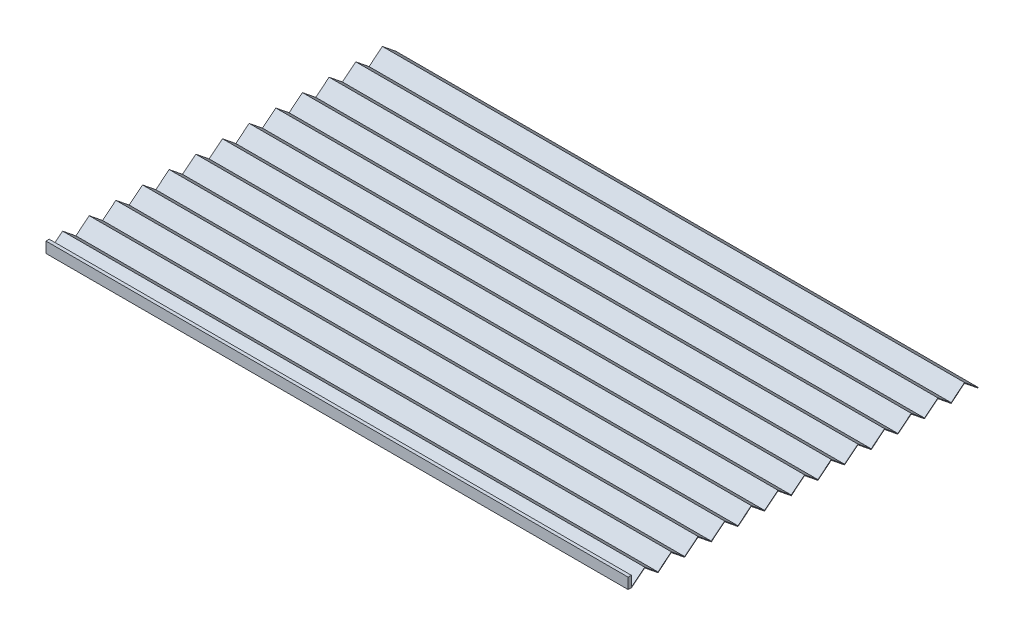
SolidWorks part; units mm, degrees
ref_plane "Front Plane" through (0, 0, 0) normal (0, 0, 1) x (1, 0, 0)
ref_plane "Top Plane" through (0, 0, 0) normal (0, 1, 0) x (1, 0, 0)
ref_plane "Right Plane" through (0, 0, 0) normal (1, 0, 0) x (0, 0, -1)
sketch "Sketch2" plane through (0, 0, 0) normal (0, 0, 1) x (1, 0, 0)
  line L1 (-270, 10) -> (270, 10)
  line L2 (-270, 10) -> (-270, 0)
  line L3 (-270, 0) -> (270, 0)
  line L4 (270, 10) -> (270, 0)
  point P4 (0, 0)
  dimension "D1" = 10
  dimension "D2" = 540
extrude "Boss-Extrude1" add sketch "Sketch2" along normal blind 3
sketch "Sketch3" plane through (270, 0, 0) normal (1, 0, 0) x (0, 0, -1)
  line L0 (0, 10) -> (321.423, 10) construction
  line L1 (0, 0) -> (321.423, 0) construction
  line L3 (0, 0) -> (12.3624, 10)
  line L4 (12.3624, 10) -> (24.7248, 0)
  line L5 (24.7248, 0) -> (37.0873, 10)
  line L6 (37.0873, 10) -> (49.4497, 0)
  line L7 (49.4497, 0) -> (61.8121, 10)
  line L8 (61.8121, 10) -> (74.1745, 0)
  line L9 (74.1745, 0) -> (86.537, 10)
  line L10 (86.537, 10) -> (98.8994, 0)
  line L11 (98.8994, 0) -> (111.2618, 10)
  line L12 (111.2618, 10) -> (123.6242, 0)
  line L13 (123.6242, 0) -> (135.9866, 10)
  line L14 (135.9866, 10) -> (148.3491, 0)
  line L15 (148.3491, 0) -> (160.7115, 10)
  line L16 (160.7115, 10) -> (173.0739, 0)
  line L17 (173.0739, 0) -> (185.4363, 10)
  line L18 (185.4363, 10) -> (197.7987, 0)
  line L20 (197.7987, 0) -> (210.1612, 10)
  line L21 (210.1612, 10) -> (222.5236, 0)
  line L22 (222.5236, 0) -> (234.886, 10)
  line L23 (234.886, 10) -> (247.2484, 0)
  line L24 (247.2484, 0) -> (259.6109, 10)
  line L25 (259.6109, 10) -> (271.9733, 0)
  line L26 (271.9733, 0) -> (284.3357, 10)
  line L27 (284.3357, 10) -> (296.6981, 0)
  line L28 (296.6981, 0) -> (309.0605, 10)
  line L29 (309.0605, 10) -> (321.423, 0)
  line L30 (321.423, 10) -> (321.423, 0) construction
  line L32 (321.423, 10) -> (321.423, 0) construction
extrude "Extrude-Thin1" add sketch "Sketch3" against normal through all thin thin type mid plane wall 0.5
